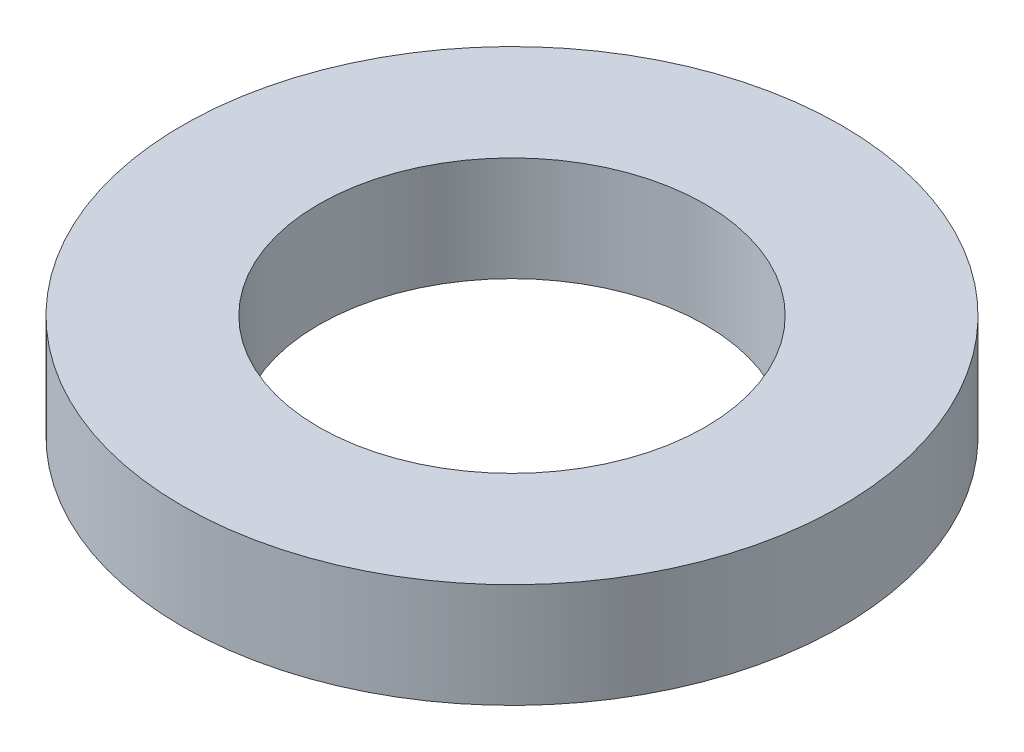
SolidWorks part; units mm, degrees
ref_plane "Front Plane" through (0, 0, 0) normal (0, 0, 1) x (1, 0, 0)
ref_plane "Top Plane" through (0, 0, 0) normal (0, 1, 0) x (1, 0, 0)
ref_plane "Right Plane" through (0, 0, 0) normal (1, 0, 0) x (0, 0, -1)
sketch "Sketch1" plane through (0, 0, 0) normal (0, 1, 0) x (1, 0, 0)
  circle A0 centre (0, 0) radius 72.5
  dimension "FLANGE_OD" = 145
extrude "Boss-Extrude1" add sketch "Sketch1" along normal blind 23
sketch "Sketch2" plane through (0, 0, 0) normal (0, 1, 0) x (1, 0, 0)
  circle A0 centre (0, 0) radius 42.5
  dimension "BORE_D" = 85
extrude "Cut-Extrude1" cut sketch "Sketch2" along normal through all
sketch "Sketch3" plane through (0, 23, 0) normal (0, 1, 0) x (1, 0, 0)
  circle A0 centre (0, 0) radius 27.4526 construction
  circle A1 centre (-27.4526, 0) radius 4.0647
  dimension "BOLT_D" = 8.1294
  dimension "BOLT_PCD" = 54.9052
extrude "Cut-Extrude2" cut sketch "Sketch3" against normal blind 20.9986 rebuild error yes
pattern_circular "CirPattern1" count 3 over 360 rebuild error yes
